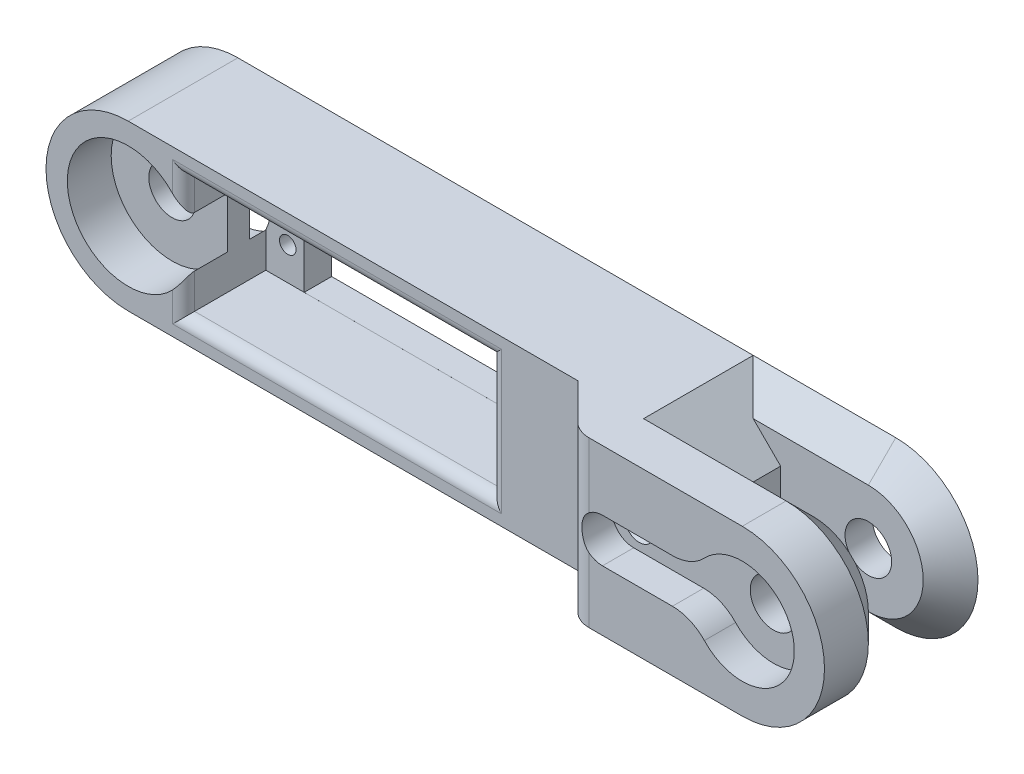
SolidWorks part; units mm, degrees
ref_plane "Front Plane" through (0, 0, 0) normal (0, 0, 1) x (1, 0, 0)
ref_plane "Top Plane" through (0, 0, 0) normal (0, 1, 0) x (1, 0, 0)
ref_plane "Right Plane" through (0, 0, 0) normal (1, 0, 0) x (0, 0, -1)
sketch "Sketch1" plane through (0, 0, 0) normal (0, 0, 1) x (1, 0, 0)
  line L0 (0, 0) -> (120, 0) construction
  line L1 (0, 15) -> (120, 15)
  line L2 (0, -15) -> (120, -15)
  circle A0 centre (0, 0) radius 15
  circle A1 centre (120, 0) radius 15
  dimension "D1" = 30
  dimension "D2" = 120
extrude "Boss-Extrude1" add sketch "Sketch1" along normal mid plane 20 contours A0 | A0 L0 A1 L1 | L0 A0 L2 A1 | A1 region at (60, 7.777, 0) region at (10.3066, -10.3066, 0) region at (60, -7.777, 0) region at (109.6934, 10.3066, 0)
sketch "Sketch3" plane through (0, 0, 10) normal (0, 0, 1) x (1, 0, 0)
  line L0 (0, 0) -> (94, 0) construction
  line L1 (90, 4.5) -> (120, 7.5)
  line L2 (90, -4.5) -> (120, -7.5)
  circle A0 centre (120, 0) radius 7.5
  circle A1 centre (90, 0) radius 4.5
  circle A2 centre (95.5, 0) radius 1.5
  circle A3 centre (120, 0) radius 4.25
  dimension "D2" = 15
  dimension "D3" = 9
  dimension "D5" = 3
  dimension "D7" = 8.5
  dimension "D1" = 120
  dimension "D4" = 30
  dimension "D6" = 24.5
extrude "Cut-Extrude5" cut sketch "Sketch3<3>" against normal blind 12 contours L1 A0 L2 A3 region at (119.2785, 7.2147, 10)
sketch "Sketch3<3>" plane through (0, 0, 10) normal (0, 0, 1) x (1, 0, 0) same geometry as "Sketch3"
extrude "Cut-Extrude6" cut sketch "Sketch3" against normal through all contours A3 region at (120, 0, 10)
sketch "Sketch4" plane through (0, 0, 10) normal (0, 0, 1) x (1, 0, 0)
  line L0 (0, 0) -> (120, 0) construction
  line L2 (59.1, -11) -> (17.1, -11)
  line L3 (59.1, -11) -> (59.1, 11)
  line L4 (59.1, 11) -> (17.1, 11)
  line L5 (17.1, -11) -> (17.1, 11)
  line L6 (59.1, -11) -> (17.1, 11) construction
  line L7 (59.1, 11) -> (17.1, -11) construction
  circle A0 centre (0, 0) radius 4.25
  circle A1 centre (0, 0) radius 11.11
  circle A2 centre (27.1, 0) radius 2.6569
  point P4 (38.1, 0)
  dimension "D3" = 8.5
  dimension "D4" = 22.22
  dimension "D1" = 22
  dimension "D2" = 42
  dimension "D5" = 27.1
  dimension "D6" = 10
extrude "Cut-Extrude8" cut sketch "Sketch4" against normal through all contours A0 | L3 L2 L5 L4
sketch "Sketch5" plane through (0, 0, -10) normal (0, 0, -1) x (-1, 0, 0)
  circle A0 centre (0, 0) radius 11.11
  dimension "D1" = 22.22
extrude "Cut-Extrude10" cut sketch "Sketch5" against normal blind 8
mirror "Mirror2" about plane through (0, 0, 0) normal (0, 0, 1) of "Cut-Extrude10"
sketch "Sketch7" plane through (0, 0, 10) normal (0, 0, 1) x (1, 0, 0)
  line L0 (38.1, 11) -> (38.1, -11) construction
  line L1 (59.1, 11) -> (17.1, 11) construction
  line L2 (59.1, -11) -> (17.1, -11) construction
  line L4 (66.1, -11.0014) -> (10.1, -11.0014)
  line L5 (66.1, -11.0014) -> (66.1, 11.0014)
  line L6 (66.1, 11.0014) -> (10.1, 11.0014)
  line L7 (10.1, -11.0014) -> (10.1, 11.0014)
  line L8 (66.1, -11.0014) -> (10.1, 11.0014) construction
  line L9 (66.1, 11.0014) -> (10.1, -11.0014) construction
  point P6 (38.1, 0)
  dimension "D2" = 56
extrude "Cut-Extrude12" cut sketch "Sketch7" against normal blind 15
sketch "Sketch8" plane through (0, 0, -5) normal (0, 0, 1) x (1, 0, 0)
  line L0 (38.1, 11.0014) -> (38.1, -11.0014) construction
  line L1 (66.1, 11.0014) -> (10.1, 11.0014) construction
  line L2 (10.1, -11.0014) -> (66.1, -11.0014) construction
  line L3 (14.1, 5) -> (14.1, -5) construction
  line L4 (62.1, 5) -> (62.1, -5) construction
  line L5 (38.1, 0) -> (25.4065, 0) construction
  line L6 (14.1, 0) -> (20.8073, 0) construction
  circle A0 centre (14.1, 5) radius 1.5
  circle A1 centre (14.1, -5) radius 1.5
  circle A2 centre (62.1, -5) radius 1.5
  circle A3 centre (62.1, 5) radius 1.5
  dimension "D1" = 3
  dimension "D2" = 10
  dimension "D3" = 48
extrude "Cut-Extrude13" cut sketch "Sketch8" against normal blind 14 contours A0 | A1 | A2 | A3 region at (14.1, 5, -5) region at (14.1, -5, -5) region at (62.1, -5, -5)
sketch "Sketch9" plane through (0, 0, 10) normal (0, 0, 1) x (1, 0, 0)
  circle A0 centre (120, 0) radius 9.5
  dimension "D1" = 19
extrude "Cut-Extrude14" cut sketch "Sketch9" against normal up to surface (12 mm away) up to face at (124.25, 0, -2)
sketch "Sketch16" plane through (0, 0, 10) normal (0, 0, 1) x (1, 0, 0)
  line L0 (120, 15) -> (80, 15)
  line L1 (0, 15) -> (120, 15) construction
  line L2 (80, 15) -> (80, -15)
  line L3 (0, -15) -> (120, -15) construction
  line L4 (80, -15) -> (120, -15)
  arc A0 (120, -15) -> (120, 15) centre (120, 0) ccw
  circle A1 centre (120, 0) radius 4.25
  circle A2 centre (120, 0) radius 9.5
  circle M2 centre (120, 0) radius 9.5
  line M9 (0, -15) -> (120, -15)
  arc M10 (120, -15) -> (120, 15) centre (120, 0) ccw
  line M11 (120, 15) -> (0, 15)
  dimension "D1" = 40
extrude "Boss-Extrude2" add sketch "Sketch16" along normal blind 8 contours L2 M11 M9 M10 M2 region at (102.8727, 0, 10)
chamfer "Chamfer1" distance 10 angle 45 1 edges at (80, 0, 18)
fillet "Fillet1" radius 5 1 edges at (90, 0, 18)
fillet "Fillet2" radius 2 5 edges at (10.1, 7.8149, 10) (10.1, -7.8149, 10) (38.1, -11.0014, 10) (66.1, 0, 10) (38.1, 11.0014, 10)
sketch "Sketch17" plane through (0, 0, 18) normal (0, 0, 1) x (1, 0, 0)
  line L0 (120, 0) -> (94.5, 0) construction
  line L1 (120, 0) -> (94.5, 0) construction
  line L2 (113.0718, -4) -> (94.5, -4)
  line L3 (113.0718, 4) -> (94.5, 4)
  arc A0 (113.0718, -4) -> (113.0718, 4) centre (120, 0) ccw
  arc A2 (94.5, 4) -> (94.5, -4) centre (94.5, 0) ccw
  point P3 (107.25, 0)
  point P10 (90.5, 0)
  dimension "D1" = 16
  dimension "D2" = 8
  dimension "D3" = 29.5
sketch "Sketch18" plane through (0, 0, -2) normal (0, 0, 1) x (1, 0, 0)
  circle A0 centre (120, 0) radius 4.25
  circle A1 centre (120, 0) radius 9.5
extrude "Boss-Extrude3" add sketch "Sketch18" along normal blind 14.3
extrude "Cut-Extrude15" cut sketch "Sketch17" against normal blind 5.7
sketch "Sketch19" plane through (0, 0, 12.3) normal (0, 0, 1) x (1, 0, 0)
  line L0 (120, 0) -> (95.5, 0) construction
  circle A0 centre (95.5, 0) radius 2.155
  dimension "D2" = 4.31
  dimension "D1" = 24.5
extrude "Cut-Extrude16" cut sketch "Sketch19" against normal blind 6
chamfer "Chamfer2" distance 0.5 angle 45 1 edges at (97.655, 0, 12.3)
fillet "Fillet3" radius 8 2 edges at (111.3832, -4, 15.15) (111.3832, 4, 15.15)
sketch "Sketch20" plane through (0, 15, 0) normal (0, 1, 0) x (1, 0, 0)
  line L0 (135, 5) -> (104, 5)
  line L1 (104, 5) -> (104, -5)
  line L2 (104, -5) -> (135, -5)
  line L3 (135, -5) -> (135, 5)
  line L4 (0, 0) -> (135, 0) construction
  line L5 (0, -10) -> (0, 10) construction
  line L6 (135, -18) -> (135, 10) construction
  point P8 (135, 0)
  point P9 (132.0576, 0)
  dimension "D1" = 31
  dimension "D2" = 10
extrude "Cut-Extrude17" cut sketch "Sketch20" against normal through all
chamfer "Chamfer4" distance 5 angle 45 6 edges at (112, -15, -5) (135, 0, -5) (112, 15, -5) (112, -15, 5) (135, 0, 5) (112, 15, 5)
chamfer "Chamfer5" distance 10 angle 45 2 edges at (104, 15, 0) (104, -15, 0)
equation "\".5.00mm\"=1"
